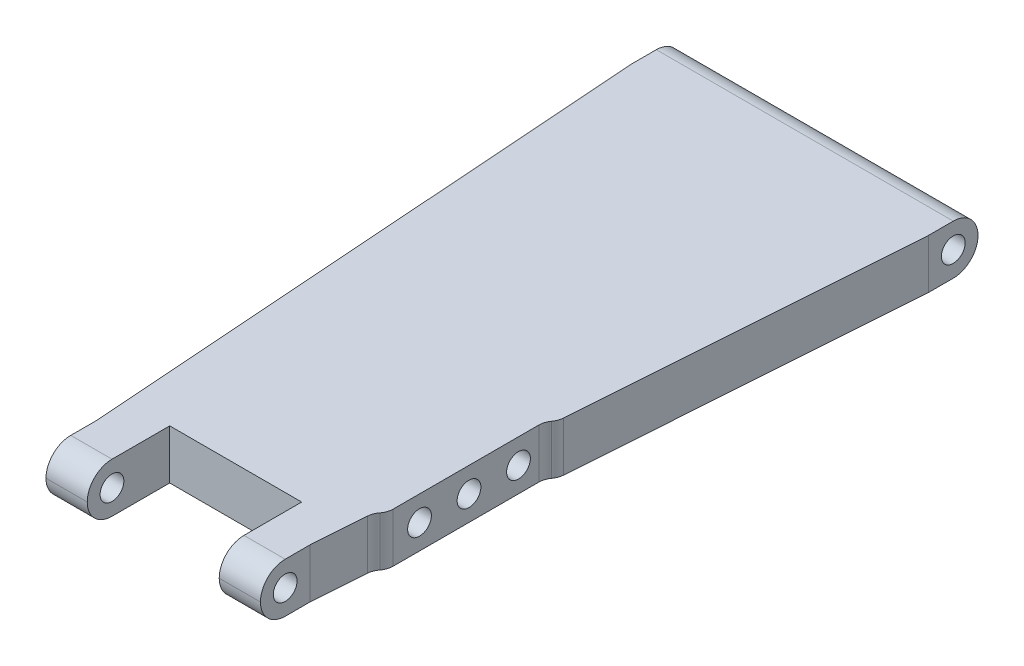
SolidWorks part; units mm, degrees
ref_plane "Front Plane" through (0, 0, 0) normal (0, 0, 1) x (1, 0, 0)
ref_plane "Top Plane" through (0, 0, 0) normal (0, 1, 0) x (1, 0, 0)
ref_plane "Right Plane" through (0, 0, 0) normal (1, 0, 0) x (0, 0, -1)
sketch "Sketch1" plane through (0, 0, 0) normal (0, 1, 0) x (1, 0, 0)
  line L0 (0, 0) -> (0, -120.65) construction
  line L1 (-28.575, 0) -> (28.575, 0) construction
  line L2 (-28.575, 4.7625) -> (-28.575, -4.7625)
  line L3 (28.575, 4.7625) -> (28.575, -4.7625)
  line L4 (-20.6375, -120.65) -> (20.6375, -120.65) construction
  line L5 (-20.6375, -115.8875) -> (-20.6375, -125.4125)
  line L6 (20.6375, -115.8875) -> (20.6375, -125.4125)
  line L7 (-28.575, -4.7625) -> (-20.6375, -115.8875)
  line L8 (28.575, -4.7625) -> (20.6375, -115.8875)
  line L9 (-20.6375, -125.4125) -> (20.6375, -125.4125)
  line L11 (-12.7, -125.4125) -> (-12.7, -109.5375)
  line L12 (-12.7, -109.5375) -> (12.7, -109.5375)
  line L13 (-28.575, 4.7625) -> (28.575, 4.7625)
  line L14 (-28.575, -4.7625) -> (28.575, -4.7625)
  line L15 (-20.6375, -115.8875) -> (20.6375, -115.8875)
  line L16 (-19.05, 4.7625) -> (-19.05, -4.7625)
  line L17 (-19.05, -4.7625) -> (19.05, -4.7625)
  line L18 (19.05, -4.7625) -> (19.05, 4.7625)
  line L19 (12.7, -109.5375) -> (12.7, -125.4125)
  line L20 (22.6786, -71.4375) -> (22.6786, -103.1875)
  line L21 (22.6786, -103.1875) -> (21.5446, -103.1875)
  line L22 (22.6786, -71.4375) -> (23.8125, -71.4375)
  point P6 (0, 0)
  point P9 (-28.575, 0)
  point P11 (28.575, 0)
  point P16 (0, -120.65)
  point P18 (-20.6375, -120.65)
  point P21 (20.6375, -120.65)
  dimension "D1" = 9.525
  dimension "D2" = 57.15
  dimension "D3" = 9.525
  dimension "D4" = 41.275
  dimension "D5" = 120.65
  dimension "D6" = 7.9375
  dimension "D7" = 7.9375
  dimension "D11" = 31.75
  dimension "D12" = 76.2
  dimension "D8" = 9.525
  dimension "D9" = 9.525
  dimension "D10" = 15.875
extrude "Boss-Extrude1" add sketch "Sketch1" along normal blind 9.525 contours L16 L13 L2 L14 | L18 L14 L3 L13 | L7 L15 L8 L14 | L15 L5 L9 | L15 L19 L9 L6 | L14 L18 L13 L16 | L21 L20 L8 region at (-23.8125, 0, 0) region at (-0.0392, 0, 55.6192) region at (0, 0, 0) region at (-16.6687, 0, 120.65) region at (23.8125, 0, 0) region at (16.6687, 0, 120.65) region at (22.3006, 0, 97.8958)
sketch "Sketch6" plane through (-28.575, 0, 0) normal (-1, 0, 0) x (0, 0, 1)
  line L0 (-4.7625, 9.525) -> (-4.7625, 0) construction
  line L1 (115.8875, 9.525) -> (125.4125, 9.525) construction
  circle A0 centre (0, 4.7625) radius 2.286
  circle A1 centre (120.65, 4.7625) radius 2.286
  point P2 (-4.7625, 4.7625)
  point P3 (0, 0)
  point P10 (120.65, 9.525)
  dimension "D1" = 4.572
extrude "Cut-Extrude2" cut sketch "Sketch6" against normal through all both and the other way through all
fillet "Fillet5" radius 4.7625 6 edges at (0, 0, -4.7625) (0, 9.525, -4.7625) (16.6687, 0, 125.4125) (-16.6687, 0, 125.4125) (-16.6687, 9.525, 125.4125) (16.6687, 9.525, 125.4125)
sketch "Sketch7" plane through (22.6786, 0, 0) normal (1, 0, 0) x (0, 0, -1)
  line L0 (-96.8375, 4.7625) -> (-87.3125, 4.7625) construction
  line L1 (-87.3125, 4.7625) -> (-77.7875, 4.7625) construction
  line L4 (-103.1875, 0) -> (-71.4375, 0)
  line L6 (-103.1875, 0) -> (-71.4375, 0)
  line L7 (-103.1875, 9.525) -> (-103.1875, 0)
  line L11 (-103.1875, 9.525) -> (-103.1875, 0)
  line L15 (-71.4375, 0) -> (-71.4375, 9.525)
  line L17 (-71.4375, 0) -> (-71.4375, 9.525)
  line L18 (-71.4375, 9.525) -> (-103.1875, 9.525)
  line L19 (-71.4375, 9.525) -> (-103.1875, 9.525)
  circle A0 centre (-96.8375, 4.7625) radius 2.286
  circle A1 centre (-87.3125, 4.7625) radius 2.286
  circle A2 centre (-77.7875, 4.7625) radius 2.286
  point P11 (-103.1875, 4.7625)
  dimension "D2" = 4.572
  dimension "D3" = 6.35
  dimension "D1" = 0
fillet "Fillet6" radius 3.175 2 edges at (21.5446, 4.7625, 103.1875) (22.6786, 4.7625, 71.4375)
fillet "Fillet7" radius 3.175 2 edges at (23.8125, 4.7625, 71.4375) (22.6786, 4.7625, 103.1875)
extrude "Cut-Extrude4" cut sketch "Sketch7" against normal blind 4.7625 contours A0 | A1 | A2 region at (22.6786, 4.7625, 96.8375) region at (22.6786, 4.7625, 87.3125) region at (22.6786, 4.7625, 77.7875)
